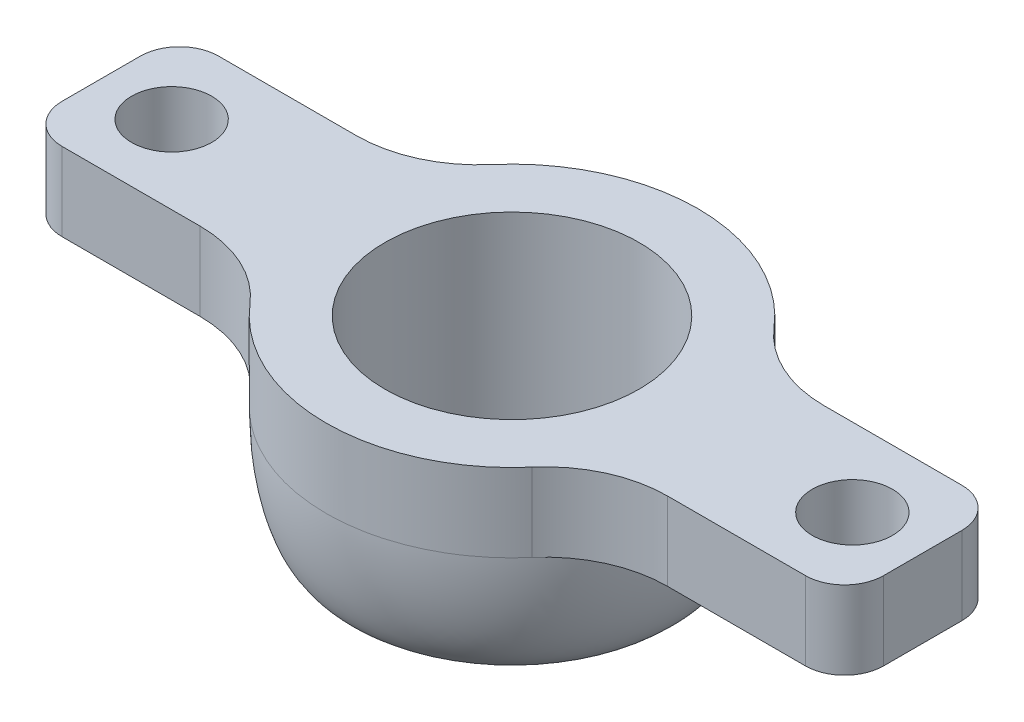
SolidWorks part; units mm, degrees
ref_plane "Front Plane" through (0, 0, 0) normal (0, 0, 1) x (1, 0, 0)
ref_plane "Top Plane" through (0, 0, 0) normal (0, 1, 0) x (1, 0, 0)
ref_plane "Right Plane" through (0, 0, 0) normal (1, 0, 0) x (0, 0, -1)
sketch "Sketch1" plane through (0, 0, 0) normal (0, 1, 0) x (1, 0, 0)
  circle A0 centre (0, 0) radius 3.25
  circle A1 centre (0, 0) radius 4.75
  dimension "D1" = 6.5
  dimension "D2" = 1.5
extrude "Boss-Extrude1" add sketch "Sketch1" along normal blind 5
sketch "Sketch2" plane through (0, 5, 0) normal (0, 1, 0) x (1, 0, 0)
  line L0 (-1.7118, -10.5508) -> (-5.4706, -9.1827)
  line L1 (-10.5, -2) -> (10.5, -2)
  line L2 (-10.5, -2) -> (-10.5, 2)
  line L3 (-10.5, 2) -> (10.5, 2)
  line L4 (10.5, -2) -> (10.5, 2)
  line L5 (-10.5, -2) -> (10.5, 2) construction
  line L6 (-10.5, 2) -> (10.5, -2) construction
  line L10 (-1.7118, -10.5508) -> (5.4706, 9.1827) [skipped]
  line L11 (5.4706, 9.1827) -> (1.7118, 10.5508) [skipped]
  line L12 (-5.4706, -9.1827) -> (1.7118, 10.5508) [skipped]
  point P0 (0, 0)
  point P13 (0, 0)
  circle M5 centre (0, 0) radius 4.75
  dimension "D1" = 21
  dimension "D3" = 4
  dimension "D2" = 2
extrude "Boss-Extrude2" add sketch "Sketch2" against normal blind 2 contours L1 L4 L3 M5 | L3 L2 L1 M5 region at (7.5514, 5, 0) region at (-7.5514, 5, 0)
sketch "Sketch3" plane through (0, 3, 0) normal (0, -1, 0) x (1, 0, 0)
  line L0 (0, 0) -> (10.5, 0)
  line L2 (10.5, 2) -> (10.5, -2) construction
  line L3 (10.5, 0) -> (0, 0)
  line L4 (0, 0) -> (8.7, 0)
  circle A2 centre (8.7, 0) radius 1.025
  circle A3 centre (-8.7, 0) radius 1.025
  point P11 (0.0022, 0)
  point P16 (0, 0)
  dimension "D2" = 2.05
  dimension "D1" = 8.7
  dimension "D3" = 2
extrude "Cut-Extrude1" cut sketch "Sketch3" against normal through all contours L3 A2 L4 | L4 A2 L3 | A3 region at (8.7, 3, 0.435) region at (8.7, 3, -0.435) region at (-8.7, 3, 0)
fillet "Fillet1" radius 3.125 4 edges at (4.3084, 4, 2) (-4.3084, 4, 2) (-4.3084, 4, -2) (4.3084, 4, -2)
fillet "Fillet2" radius 1 4 edges at (-10.5, 4, -2) (-10.5, 4, 2) (10.5, 4, 2) (10.5, 4, -2)
fillet "Fillet3" radius 1 1 edges at (0, 0, 4.75) second distance 3 first distance on face at (0, 0, 4.75)
